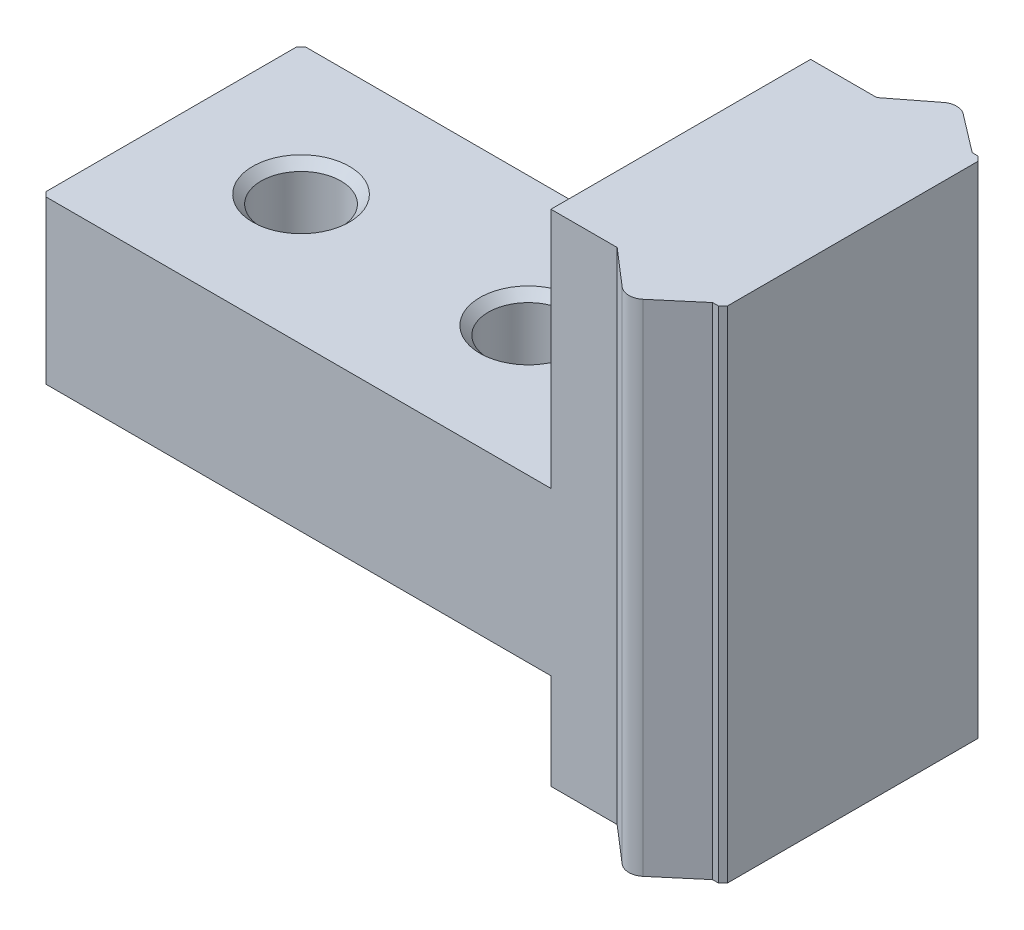
SolidWorks part; units mm, degrees
ref_plane "前视基准面" through (0, 0, 0) normal (0, 0, 1) x (1, 0, 0)
ref_plane "上视基准面" through (0, 0, 0) normal (0, 1, 0) x (1, 0, 0)
ref_plane "右视基准面" through (0, 0, 0) normal (1, 0, 0) x (0, 0, -1)
ref_plane "Plane1" through (0, -3, 0) normal (0, 1, 0) x (1, 0, 0)
sketch "Sketch1" plane through (0, -3, 0) normal (0, 1, 0) x (1, 0, 0)
  line L0 (-51.8, -4) -> (-49.76, -4)
  line L1 (-49.76, -4) -> (-48.6268, -4.9785)
  line L2 (-47.9765, -4.9813) -> (-46.82, -4)
  line L3 (-46.82, -4) -> (-46.6414, -4)
  line L4 (-46.6414, -4) -> (-46.5, -3.8586)
  line L5 (-46.5, -3.8586) -> (-46.5, 3.8586)
  line L6 (-46.5, 3.8586) -> (-46.6414, 4)
  line L7 (-46.6414, 4) -> (-46.82, 4)
  line L8 (-46.82, 4) -> (-47.9968, 4.8976)
  line L9 (-48.6065, 4.895) -> (-49.76, 4)
  line L10 (-49.76, 4) -> (-51.8, 4)
  line L11 (-51.8, 4) -> (-51.8, -4)
  arc A0 (-48.6268, -4.9785) -> (-47.9765, -4.9813) centre (-48.3, -4.6) ccw
  arc A1 (-47.9968, 4.8976) -> (-48.6065, 4.895) centre (-48.3, 4.5) ccw
extrude "Boss-Extrude1" add sketch "Sketch1" against normal blind 15.4
ref_plane "Plane2" through (0, -3.75, 0) normal (0, 1, 0) x (1, 0, 0)
ref_plane "Plane3" through (0, -9.55, 0) normal (0, 1, 0) x (1, 0, 0)
ref_plane "Plane4" through (0, -6.8, 0) normal (0, 1, 0) x (1, 0, 0)
ref_plane "Plane5" through (0, -14.8, 0) normal (0, 1, 0) x (1, 0, 0)
ref_plane "Plane6" through (0, -10.45, 0) normal (0, 1, 0) x (1, 0, 0)
sketch "Sketch2" plane through (0, -10.45, 0) normal (0, 1, 0) x (1, 0, 0)
  line L0 (-67.5, 3.8586) -> (-67.5, -3.8586)
  line L1 (-67.5, -3.8586) -> (-67.3586, -4)
  line L2 (-67.3586, -4) -> (-51.8, -4)
  line L3 (-51.8, -4) -> (-51.8, 4)
  line L4 (-51.8, 4) -> (-67.3586, 4)
  line L5 (-67.3586, 4) -> (-67.5, 3.8586)
extrude "Boss-Extrude2" add sketch "Sketch2" against normal blind 5
sketch "Sketch3" plane through (0, 0, 0) normal (0, 0, 1) x (1, 0, 0)
  line L0 (-63.5, -15.45) -> (-65, -15.45)
  line L1 (-65, -15.45) -> (-64.7295, -15.1795)
  line L2 (-64.7295, -15.1795) -> (-64.7295, -10.7105)
  line L3 (-64.7295, -10.7105) -> (-65, -10.44)
  line L4 (-65, -10.44) -> (-63.5, -10.44)
  line L5 (-63.5, -10.44) -> (-63.5, -15.45)
  line L6 (-63.5, -10.44) -> (-63.5, -15.45) construction
revolve "Cut-Revolve1" cut sketch "Sketch3" angle 360 about L6 reverse direction yes
cosmetic thread "Cosmetic Thread1" parameters "D1"=5, "D2"=6.836
sketch "Sketch4" plane through (0, 0, 0) normal (0, 0, 1) x (1, 0, 0)
  line L0 (-56.5, -15.45) -> (-58, -15.45)
  line L1 (-58, -15.45) -> (-57.7295, -15.1795)
  line L2 (-57.7295, -15.1795) -> (-57.7295, -10.7105)
  line L3 (-57.7295, -10.7105) -> (-58, -10.44)
  line L4 (-58, -10.44) -> (-56.5, -10.44)
  line L5 (-56.5, -10.44) -> (-56.5, -15.45)
  line L6 (-56.5, -10.44) -> (-56.5, -15.45) construction
revolve "Cut-Revolve2" cut sketch "Sketch4" angle 360 about L6 reverse direction yes
cosmetic thread "Cosmetic Thread2" parameters "D1"=5, "D2"=6.836
ref_plane "Plane7" through (0, -12.95, 0) normal (0, 1, 0) x (1, 0, 0)
ref_plane "for body XY" through (0, 0, 0) normal (0, 1, 0) x (1, 0, 0)
ref_plane "for body XZ" through (0, 0, 0) normal (0, 0, 1) x (1, 0, 0)
ref_plane "for body YZ" through (-48.3, 0, 0) normal (1, 0, 0) x (0, 0, -1)
ref_axis "for body X" through (-80.9, 0, 0) along (1, 0, 0)
ref_axis "for body Y" through (-48.3, 0, 50) along (0, 0, -1)
ref_axis "for body Z" through (-48.3, 50, 0) along (0, -1, 0)
sketch3d "for body"
  point P0 (-48.3, 0, 0)
scale "缩放比例1" bodies to scale 105 scale about centroid uniform scaling yes scale factor 2.5
equation "\"Dummy1\"= \"图号代码\""
equation "\"Dummy2\"= \"名称代码\""
